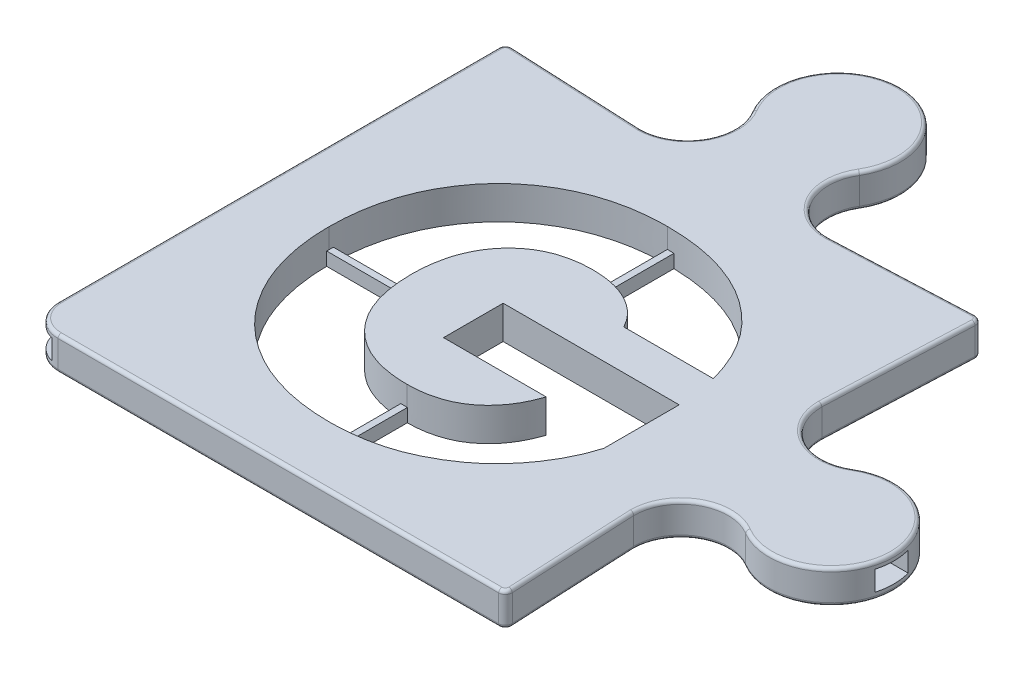
SolidWorks part; units mm, degrees
ref_plane "Front Plane" through (0, 0, 0) normal (0, 0, 1) x (1, 0, 0)
ref_plane "Top Plane" through (0, 0, 0) normal (0, 1, 0) x (1, 0, 0)
ref_plane "Right Plane" through (0, 0, 0) normal (1, 0, 0) x (0, 0, -1)
sketch "Sketch1" plane through (0, 0, 0) normal (0, 1, 0) x (1, 0, 0)
  line L0 (-31, -36) -> (37, -36) construction
  line L1 (-36, 37) -> (-36, -31) construction
  line L2 (-14.1421, 36) -> (-36, 37) construction
  line L3 (37, 37) -> (14.1421, 36) construction
  line L4 (36, 13.1421) -> (37, 37) construction
  line L5 (37, -36) -> (36, -15.1421) construction
  line L6 (-35.4, 36.3719) -> (-35.4, -31)
  line L7 (-36, 36) -> (36, 36) construction
  line L8 (-36, 36) -> (-36, -36) construction
  line L9 (-36, -36) -> (36, -36) construction
  line L10 (36, 36) -> (36, -36) construction
  line L11 (-31, -35.4) -> (36.3705, -35.4)
  line L12 (36.3705, -35.4) -> (35.4, -15.1568)
  line L13 (35.4, 13.155) -> (36.3732, 36.372)
  line L14 (36.3732, 36.372) -> (14.1555, 35.4)
  line L15 (-14.1562, 35.4) -> (-35.4, 36.3719)
  line L16 (-30, -24) -> (30, -24) construction
  line L17 (-30, 29) -> (30, 29) construction
  line L18 (-30, 29) -> (-30, -31) construction
  line L19 (-30, -31) -> (30, -31) construction
  line L20 (30, 29) -> (30, -31) construction
  line L21 (-30, 24) -> (30, 24) construction
  line L22 (-30, 24) -> (-30, -26) construction
  line L23 (-30, -26) -> (30, -26) construction
  line L24 (30, 24) -> (30, -26) construction
  arc A0 (-36, -31) -> (-31, -36) centre (-31, -31) ccw construction
  arc A1 (-14.1421, 36) -> (-8.571, 45.8485) centre (-14.1421, 42.5) ccw construction
  arc A2 (8.571, 45.8485) -> (-8.571, 45.8485) centre (0, 51) ccw construction
  arc A3 (8.571, 45.8485) -> (14.1421, 36) centre (14.1421, 42.5) ccw construction
  arc A4 (36, 13.1421) -> (45.8485, 7.571) centre (42.5, 13.1421) ccw construction
  arc A5 (45.8485, -9.571) -> (45.8485, 7.571) centre (51, -1) ccw construction
  arc A6 (45.8485, -9.571) -> (36, -15.1421) centre (42.5, -15.1421) ccw construction
  arc A7 (-35.4, -31) -> (-31, -35.4) centre (-31, -31) ccw
  arc A8 (46.1576, -9.0567) -> (35.4, -15.1568) centre (42.5, -15.1421) ccw
  arc A9 (46.1576, -9.0567) -> (46.1576, 7.0567) centre (51, -1) ccw
  arc A10 (35.4, 13.155) -> (46.1576, 7.0567) centre (42.5, 13.1421) ccw
  arc A11 (8.0567, 46.1576) -> (14.1555, 35.4) centre (14.1421, 42.5) ccw
  arc A12 (8.0567, 46.1576) -> (-8.0567, 46.1576) centre (0, 51) ccw
  arc A13 (-14.1562, 35.4) -> (-8.0567, 46.1576) centre (-14.1421, 42.5) ccw
  point P32 (36, 0)
  point P34 (0, 36)
  dimension "D5" = 6.5
  dimension "D6" = 10
  dimension "D7" = 6.5
  dimension "D13" = 5
  dimension "D9" = 10
  dimension "D11" = 6.5
  dimension "D12" = 6.5
  dimension "D1" = 72
  dimension "D2" = 1
  dimension "D3" = 1
  dimension "D4" = 15
  dimension "D8" = 1
  dimension "D10" = 35
  dimension "D14" = 15
  dimension "D15" = 36
  dimension "D16" = 1
  dimension "D18" = 60
  dimension "D19" = 60
  dimension "D20" = 5
  dimension "D21" = 6
  dimension "D22" = 5
  dimension "D23" = 50
  dimension "D24" = 2
  dimension "D17" = 0.6
extrude "Boss-Extrude1" add sketch "Sketch1" along normal blind 5
sketch "Sketch6" plane through (0, 0, 0) normal (0, -1, 0) x (1, 0, 0)
  line L0 (-35.4, -36.3719) -> (-35.4, 31) construction
  line L1 (-35.4, 17.9) -> (-27.4, 17.9)
  line L2 (-35.4, 17.9) -> (-35.4, -16.1)
  line L3 (-35.4, -16.1) -> (-27.4, -16.1)
  line L4 (-27.4, 17.9) -> (-27.4, -16.1)
  line L5 (-31, 35.4) -> (36.3705, 35.4) construction
  line L6 (-35.4, 14.65) -> (-30.4, 14.65)
  line L7 (-35.4, 14.65) -> (-35.4, -12.85)
  line L8 (-35.4, -12.85) -> (-30.4, -12.85)
  line L9 (-30.4, 14.65) -> (-30.4, -12.85)
  point P15 (-27.4, 0.9)
  point P16 (-30.4, 0.9)
  line M28 (-35.4, 31) -> (-35.4, -36.3719)
  dimension "D1" = 8
  dimension "D2" = 20.75
  dimension "D3" = 27.5
  dimension "D4" = 5
  dimension "D5" = 34
extrude "Cut-Extrude3" cut sketch "Sketch6" against normal blind 3 from offset 1 contours L6 L9 L8 L3 L4 L1 M28 | L9 L6 L2 L8 region at (-29.8665, 0, 0.9) region at (-32.9, 0, 0.9) offset against normal yes
extrude "Cut-Extrude4" cut sketch "Sketch6<3>" against normal up to next contours L9 L6 L2 L8 region at (-32.9, 0, 0.9)
sketch "Sketch6<3>" plane through (0, 0, 0) normal (0, -1, 0) x (1, 0, 0) same geometry as "Sketch6"
sketch "Sketch8" plane through (0, 0, 0) normal (0, -1, 0) x (1, 0, 0)
  line L1 (-2.5, -51.4) -> (2.5, -51.4)
  line L2 (-2.5, -51.4) -> (-2.5, -60.4)
  line L3 (-2.5, -60.4) -> (2.5, -60.4)
  line L4 (2.5, -51.4) -> (2.5, -60.4)
  line L5 (51.4, 3.5) -> (60.4, 3.5)
  line L6 (51.4, 3.5) -> (51.4, -1.5)
  line L7 (51.4, -1.5) -> (60.4, -1.5)
  line L8 (60.4, 3.5) -> (60.4, -1.5)
  arc A0 (-8.0567, -46.1576) -> (8.0567, -46.1576) centre (0, -51) ccw construction
  arc A1 (46.1576, -7.0567) -> (46.1576, 9.0567) centre (51, 1) ccw construction
  point P4 (0, -60.4)
  point P13 (60.4, 1)
  dimension "D1" = 5
  dimension "D2" = 9
  dimension "D3" = 5
  dimension "D4" = 9
extrude "Cut-Extrude5" cut sketch "Sketch8" against normal blind 3 from offset 1 offset against normal yes
sketch "Sketch9" plane through (0, 0, 0) normal (0, -1, 0) x (1, 0, 0)
  line L0 (-31, 35.4) -> (36.3705, 35.4) construction
  line L1 (-35.4, 14.65) -> (-35.4, 31) construction
  line L2 (-31.7636, 35.3332) -> (-35.4, 31) construction
  line L3 (-33.2571, 29.735) -> (-30.0429, 33.565) construction
  line L4 (-30.0429, 33.565) -> (-33.2571, 29.735) construction
  line L5 (-30.0429, 33.565) -> (-32.7119, 35.8048)
  line L6 (-33.2571, 29.735) -> (-35.926, 31.9747)
  line L7 (-32.7119, 35.8048) -> (-35.926, 31.9747)
  circle A0 centre (-31.65, 31.65) radius 2.5
  arc A1 (-31, 35.4) -> (-35.4, 31) centre (-31, 31) ccw construction
  arc M41 (-31, 35.4) -> (-35.4, 31) centre (-31, 31) ccw
  dimension "D1" = 5
  dimension "D3" = 3.75
  dimension "D4" = 5.6569
  dimension "D2" = 3.75
extrude "Cut-Extrude6" cut sketch "Sketch9" against normal blind 3 from offset 1 contours A0 L5 L6 M41 | A0 L5 region at (-33.6239, 0, 33.3064) region at (-31.65, 0, 31.65) offset against normal yes
sketch "Sketch11" plane through (-35.4, 0, 0) normal (-1, 0, 0) x (0, 0, 1)
  line L0 (-13.155, 0) -> (-36.372, 0) construction
  line L1 (-25.1, 3) -> (-19.1, 3)
  line L2 (-25.1, 3) -> (-25.1, 1.5)
  line L3 (-25.1, 1.5) -> (-19.1, 1.5)
  line L4 (-19.1, 3) -> (-19.1, 1.5)
  line L5 (-16.1, 4) -> (-16.1, 1) construction
  line L6 (35.4, 0) -> (15.1568, 0) construction
  line L7 (20.9, 3) -> (26.9, 3)
  line L8 (20.9, 3) -> (20.9, 1.5)
  line L9 (20.9, 1.5) -> (26.9, 1.5)
  line L10 (26.9, 3) -> (26.9, 1.5)
  line L12 (17.9, 4) -> (17.9, 1) construction
  dimension "D1" = 3
  dimension "D2" = 1.5
  dimension "D3" = 3
  dimension "D4" = 6
  dimension "D5" = 3
  dimension "D6" = 1.5
  dimension "D7" = 6
  dimension "D8" = 3
fillet "Fillet1" radius 0.5 17 edges at (-35.4, 0, 22.825) (-34.1113, 0, 34.1113) (2.6853, 0, 35.4) (35.8853, 0, 25.2784) (38.9978, 0, 8.966) (60.4, 0, 1) (38.9986, 0, -6.9655) (35.8866, 0, -24.7635) (25.2643, 0, -35.886) (7.9657, 0, -38.9984) (0, 0, -60.4) (-7.9658, 0, -38.9981) (-24.7781, 0, -35.886) (-35.4, 0, -24.611) (-32.9, 0, -12.85) (-30.4, 0, 0.9) (-32.9, 0, 14.65)
fillet "Fillet2" radius 0.5 13 edges at (-7.9658, 5, -38.9981) (0, 5, -60.4) (7.9657, 5, -38.9984) (25.2643, 5, -35.886) (35.8866, 5, -24.7635) (38.9986, 5, -6.9655) (60.4, 5, 1) (38.9978, 5, 8.966) (35.8853, 5, 25.2784) (2.6853, 5, 35.4) (-34.1113, 5, 34.1113) (-35.4, 5, -2.686) (-24.7781, 5, -35.886)
fillet "Fillet3" radius 1 9 edges at (36.2202, 0.1464, -36.2187) (36.2202, 4.8536, -36.2187) (36.3732, 2.5, -36.372) (-35.2536, 0.1464, -36.2186) (-35.2536, 4.8536, -36.2186) (36.2169, 0.1464, 35.2536) (36.2169, 4.8536, 35.2536) (36.3705, 2.5, 35.4) (-35.4, 2.5, -36.3719)
extrude "Cut-Extrude9" cut sketch "Sketch11" against normal blind 3
chamfer "Chamfer1" distance 1 angle 50 2 edges at (-35.4, 1.5, 23.9) (-35.4, 1.5, -22.1) first distance on face at (-35.4, 2.25, -22.1)
sketch "Sketch12" plane through (0, 5, 0) normal (0, 1, 0) x (1, 0, 0)
  text T0 "G" font "Poppins" height 50
extrude "Cut-Extrude10" cut sketch "Sketch12" against normal through all
sketch "Sketch13" plane through (0, 0, 0) normal (0, -1, 0) x (1, 0, 0)
  line L0 (-1.6076, -2.2049) -> (24.8866, -2.2049) construction
  line L1 (13.8397, 6.7708) -> (12.8397, 6.7708)
  line L2 (13.8397, 6.7708) -> (13.8397, -2.2049)
  line L3 (13.8397, -2.2049) -> (12.8397, -2.2049)
  line L4 (12.8397, 6.7708) -> (12.8397, -2.2049)
  line L5 (1.7312, 15.6022) -> (1.7312, 26.3425) construction
  line L6 (1.7312, -13.2786) -> (1.7312, -24.554) construction
  line L7 (-12.2939, 0.8898) -> (-24.6908, 0.8898) construction
  line L8 (1.7739, 14.5151) -> (0.7739, 14.5151)
  line L9 (1.7739, 14.5151) -> (1.7739, 27.9264)
  line L10 (1.7739, 27.9264) -> (0.7739, 27.9264)
  line L11 (0.7739, 14.5151) -> (0.7739, 27.9264)
  line L12 (1.742, -12.1455) -> (0.742, -12.1455)
  line L13 (1.742, -12.1455) -> (1.742, -25.5886)
  line L14 (1.742, -25.5886) -> (0.742, -25.5886)
  line L15 (0.742, -12.1455) -> (0.742, -25.5886)
  line L16 (24.8866, -2.2049) -> (24.8866, 9.1204) construction
  line L17 (-25.3869, 1.2753) -> (-11.3875, 1.2753)
  line L18 (-25.3869, 1.2753) -> (-25.3869, 0.2753)
  line L19 (-25.3869, 0.2753) -> (-11.3875, 0.2753)
  line L20 (-11.3875, 1.2753) -> (-11.3875, 0.2753)
  line L21 (13.4705, 7.7708) -> (24.8866, 7.7708)
  line L22 (13.4705, 7.7708) -> (13.4705, 6.7708)
  line L23 (13.4705, 6.7708) -> (24.8866, 6.7708)
  line L24 (24.8866, 7.7708) -> (24.8866, 6.7708)
  line L25 (13.8397, 6.7708) -> (-1.6076, 6.7708) construction
  line L27 (-1.6076, -2.2049) -> (-0.6076, -2.2049)
  line L28 (-1.6076, -2.2049) -> (-1.6076, 6.7708)
  line L29 (-1.6076, 6.7708) -> (-0.6076, 6.7708)
  line L30 (-0.6076, -2.2049) -> (-0.6076, 6.7708)
  line L31 (24.8866, -2.2049) -> (23.8866, -2.2049)
  line L32 (24.8866, -2.2049) -> (24.8866, 11.8466)
  line L33 (24.8866, 11.8466) -> (23.8866, 11.8466)
  line L34 (23.8866, -2.2049) -> (23.8866, 11.8466)
  line L35 (9.9454, -9.1921) -> (24.0313, -9.1921)
  line L36 (9.9454, -9.1921) -> (9.9454, -8.1921)
  line L37 (9.9454, -8.1921) -> (24.0313, -8.1921)
  line L38 (24.0313, -9.1921) -> (24.0313, -8.1921)
  spline S0 degree 3 poles (24.8866, 9.1204) (24.6382, 9.872) (24.1388, 11.3829) (23.0903, 13.5517) (21.8163, 15.6424) (20.3149, 17.6404) (18.5862, 19.5031) (16.637, 21.2038) (14.4431, 22.6767) (12.4776, 23.7707) (10.8015, 24.5195) (9.4951, 25.015) (8.1451, 25.429) (6.7577, 25.765) (5.328, 26.0392) (3.8576, 26.2174) (2.348, 26.3359) (1.3296, 26.3523) (0.8141, 26.3607) knots 0 0 0 0 0.074673 0.150105 0.226804 0.305546 0.385633 0.466328 0.549174 0.634664 0.67836 0.72239 0.7665 0.811571 0.857112 0.903854 0.951337 1 1 1 1 construction
  spline S1 degree 3 poles (10.573, -8.1921) (10.3344, -8.5922) (9.8637, -9.382) (8.945, -10.4144) (7.8839, -11.2971) (6.6811, -12.0291) (5.3565, -12.6067) (3.9157, -13.0198) (2.3651, -13.2693) (1.2925, -13.2986) (0.742, -13.3137) knots 0 0 0 0 0.119643 0.236127 0.353477 0.47368 0.597163 0.724151 0.858411 1 1 1 1 construction
  spline S3 degree 3 poles (1.7312, 15.6022) (2.0992, 15.5984) (2.8231, 15.5909) (3.8827, 15.4687) (4.8998, 15.2985) (5.8717, 15.0501) (6.8024, 14.73) (7.6901, 14.3401) (8.5301, 13.8718) (9.3266, 13.3341) (10.0736, 12.7294) (10.7734, 12.0609) (11.4186, 11.3342) (12.0116, 10.5394) (12.5553, 9.6903) (13.0432, 8.7732) (13.4744, 7.7974) (13.7168, 7.116) (13.8397, 6.7708) knots 0 0 0 0 0.068307 0.134409 0.19788 0.259789 0.320532 0.38053 0.43966 0.498952 0.558848 0.617975 0.678547 0.73917 0.802012 0.865676 0.931959 1 1 1 1 construction
  dimension "D1" = 1
  dimension "D2" = 1
  dimension "D3" = 1
  dimension "D4" = 1
  dimension "D5" = 1
  dimension "D6" = 1
  dimension "D7" = 1
  dimension "D8" = 1
  dimension "D10" = 0.6146
extrude "Boss-Extrude18" add sketch "Sketch13" against normal blind 2 contours L35 L38 L37 L36 | L13 L12 L15 L14 | L18 L17 L20 L19 | L9 L8 L11 L10
